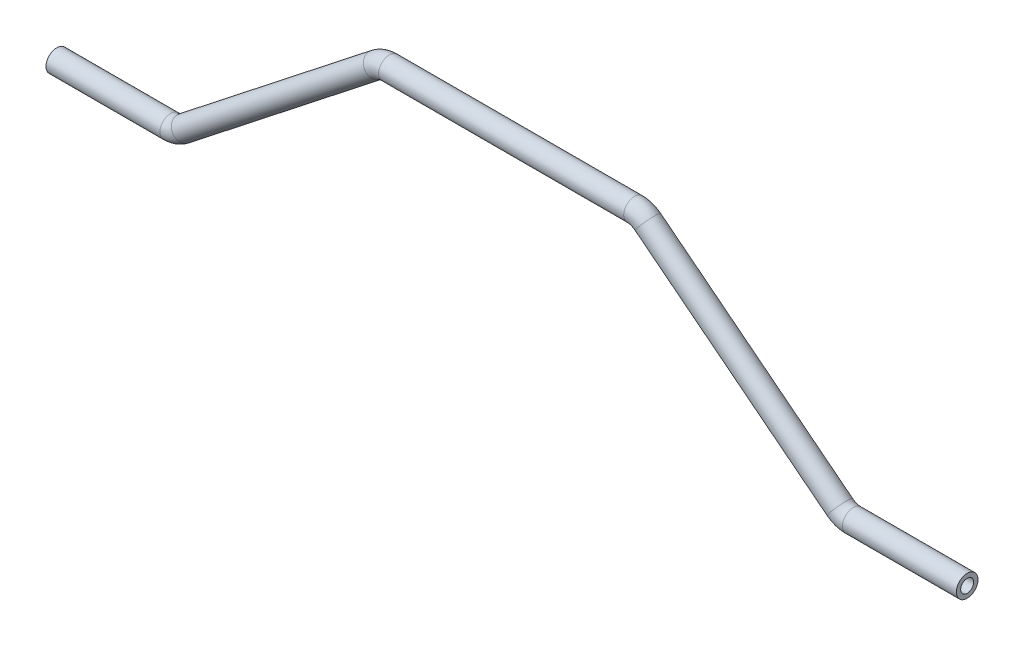
SolidWorks part; units mm, degrees
ref_plane "Front Plane" through (0, 0, 0) normal (0, 0, 1) x (1, 0, 0)
ref_plane "Top Plane" through (0, 0, 0) normal (0, 1, 0) x (1, 0, 0)
ref_plane "Right Plane" through (0, 0, 0) normal (1, 0, 0) x (0, 0, -1)
sketch "Sketch1" plane through (0, 0, 0) normal (0, 0, 1) x (1, 0, 0)
  line L0 (-56.5403, 0) -> (56.5403, 0)
  line L1 (62.72, -2.138) -> (151.28, -71.7477)
  line L2 (157.4597, -73.8857) -> (210, -73.8857)
  line L3 (0, 0) -> (0, -176.8485) construction
  line L4 (-157.4597, -73.8857) -> (-210, -73.8857)
  line L5 (-62.72, -2.138) -> (-151.28, -71.7477)
  arc A0 (157.4597, -73.8857) -> (151.28, -71.7477) centre (157.4597, -63.8857) cw
  arc A1 (62.72, -2.138) -> (56.5403, 0) centre (56.5403, -10) ccw
  arc A2 (-62.72, -2.138) -> (-56.5403, 0) centre (-56.5403, -10) cw
  arc A3 (-157.4597, -73.8857) -> (-151.28, -71.7477) centre (-157.4597, -63.8857) ccw
  point P10 (60, 0)
  dimension "D3" = 10
  dimension "D1" = 60
  dimension "D2" = 210
ref_plane "Plane1" through (210, -73.8857, 0) normal (1, 0, 0) x (0, 0, -1)
sketch "Sketch2" plane through (210, -73.8857, 0) normal (1, 0, 0) x (0, 0, -1)
  line L0 (0, 73.8857) -> (0, -102.9627) construction
  circle A0 centre (0, -0.0425) radius 5
  circle A1 centre (0, -0.0425) radius 3
  dimension "D1" = 2
sweep "Sweep1" add profiles "Sketch2" path "Sketch1"
